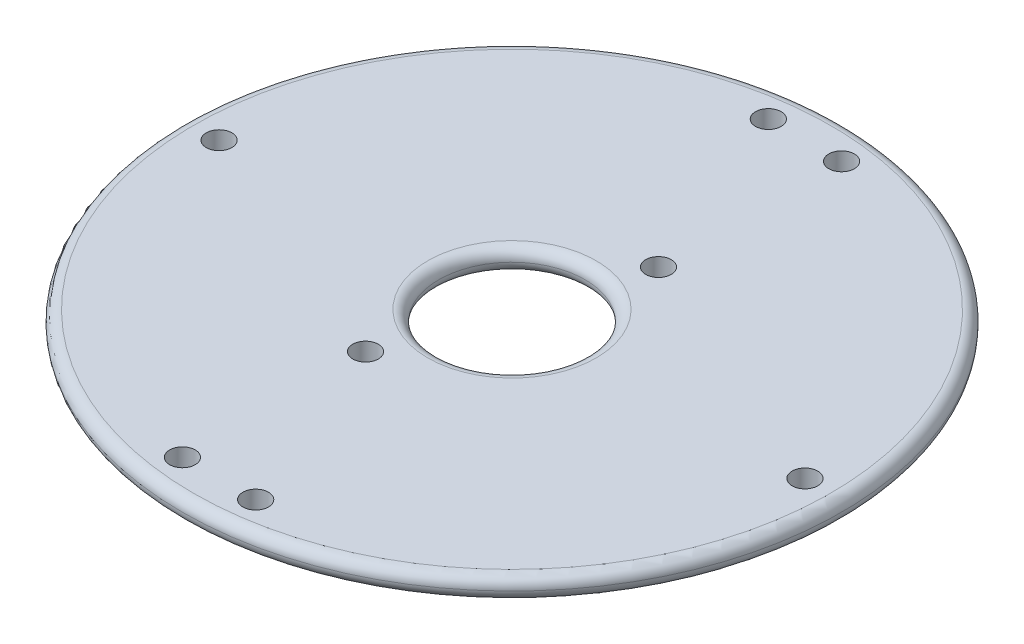
SolidWorks part; units mm, degrees
ref_plane "Front Plane" through (0, 0, 0) normal (0, 0, 1) x (1, 0, 0)
ref_plane "Top Plane" through (0, 0, 0) normal (0, 1, 0) x (1, 0, 0)
ref_plane "Right Plane" through (0, 0, 0) normal (1, 0, 0) x (0, 0, -1)
sketch "Sketch1" plane through (0, 0, 0) normal (0, 1, 0) x (1, 0, 0)
  circle A0 centre (0, 0) radius 45
extrude "Boss-Extrude1" add sketch "Sketch1" along normal blind 3
sketch "Sketch2" plane through (0, 3, 0) normal (0, 1, 0) x (1, 0, 0)
  circle A2 centre (-5, -40) radius 1.75
  circle A3 centre (5, -40) radius 1.75
  circle A4 centre (-5, 40) radius 1.75
  circle A5 centre (5, 40) radius 1.75
  circle A6 centre (-40, 0) radius 1.75
  circle A7 centre (40, 0) radius 1.75
  circle A8 centre (-5, -15) radius 1.75
  circle A9 centre (5, 15) radius 1.75
  point P1 (0, 0)
  point P2 (0, 0)
  point P3 (0, 0)
  point P5 (0, 0)
extrude "Cut-Extrude1" cut sketch "Sketch2" against normal blind 10 contours A4 | A5 | A6 | A8 | A9 | A7 | A2 | A3 region at (-5, 3, 40) region at (5, 3, 40) region at (-5, 3, -40) region at (5, 3, -40) region at (-40, 3, 0) region at (40, 3, 0) region at (-5, 3, 15) region at (5, 3, -15)
sketch "Sketch3" plane through (0, 3, 0) normal (0, 1, 0) x (1, 0, 0)
  circle A0 centre (0, 0) radius 10
extrude "Cut-Extrude2" cut sketch "Sketch3" against normal blind 5
fillet "Fillet1" radius 1.5 2 edges at (0, 0, 45) (0, 3, 45)
fillet "Fillet2" radius 1.5 2 edges at (0, 0, 10) (0, 3, 10)
